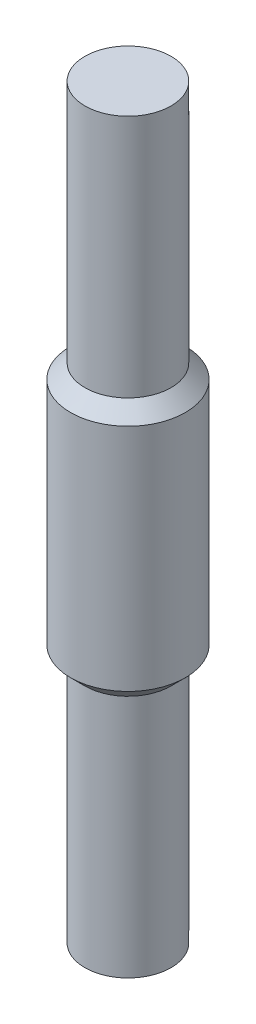
SolidWorks part; units mm, degrees
ref_plane "前视基准面" through (0, 0, 0) normal (0, 0, 1) x (1, 0, 0)
ref_plane "上视基准面" through (0, 0, 0) normal (0, 1, 0) x (1, 0, 0)
ref_plane "右视基准面" through (0, 0, 0) normal (1, 0, 0) x (0, 0, -1)
sketch "草图1" plane through (0, 0, 0) normal (0, 1, 0) x (1, 0, 0)
  circle A0 centre (0, 0) radius 2
  dimension "D1" = 4
extrude "凸台-拉伸1" add sketch "草图1" along normal blind 10
sketch "草图2" plane through (0, 0, 0) normal (0, -1, 0) x (1, 0, 0)
  circle A0 centre (0, 0) radius 1.5
  dimension "D1" = 3
extrude "凸台-拉伸2" add sketch "草图2" along normal blind 8
sketch "草图3" plane through (0, 10, 0) normal (0, 1, 0) x (1, 0, 0)
  circle A0 centre (0, 0) radius 1.5
  dimension "D1" = 3
extrude "凸台-拉伸3" add sketch "草图3" along normal blind 8
chamfer "倒角1" distance 1 angle 45 2 edges at (0, 0, 2) (0, 10, 2)
